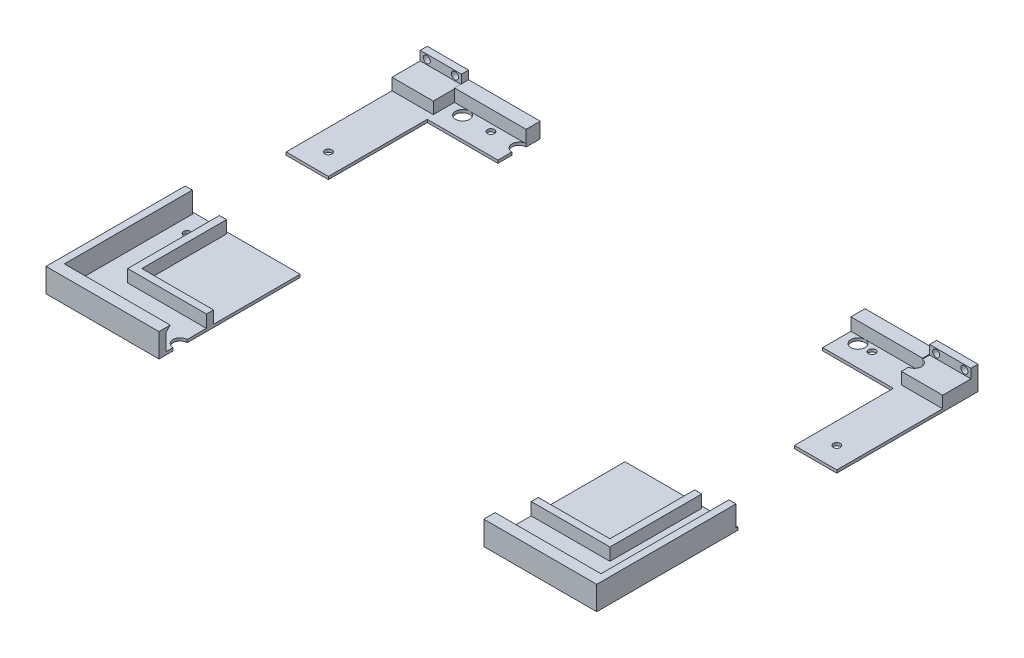
SolidWorks part; units mm, degrees
other "Laptop Holder C"
other "Laptop Holder B"
other "Laptop Holder A"
other "Laptop Holder D"
ref_plane "Front Plane" through (0, 0, 0) normal (0, 0, 1) x (1, 0, 0)
ref_plane "Top Plane" through (0, 0, 0) normal (0, 1, 0) x (1, 0, 0)
ref_plane "Right Plane" through (0, 0, 0) normal (1, 0, 0) x (0, 0, -1)
sketch "Sketch1" plane through (0, 0, 0) normal (0, 1, 0) x (1, 0, 0)
  line L1 (-195, -135) -> (195, -135)
  line L2 (-195, -135) -> (-195, 135)
  line L3 (-195, 135) -> (195, 135)
  line L4 (195, -135) -> (195, 135)
  line L5 (-195, -135) -> (195, 135) construction
  line L6 (-195, 135) -> (195, -135) construction
  point P0 (0, 0)
  dimension "D1" = 390
  dimension "D2" = 270
extrude "Boss-Extrude1" add sketch "Sketch1" along normal blind 16.825
sketch "Sketch2" plane through (0, 16.825, 0) normal (0, 1, 0) x (1, 0, 0)
  line L0 (195, 135) -> (-195, 135) construction
  line L1 (-165.75, -96.4) -> (165.75, -96.4)
  line L2 (-165.75, -96.4) -> (-165.75, 135)
  line L3 (-165.75, 135) -> (165.75, 135)
  line L4 (165.75, -96.4) -> (165.75, 135)
  line L5 (-165.75, -96.4) -> (165.75, 135) construction
  line L6 (-165.75, 135) -> (165.75, -96.4) construction
  point P0 (0, 19.3)
  dimension "D1" = 331.5
  dimension "D2" = 231.4
extrude "Cut-Extrude1" cut sketch "Sketch2" against normal blind 14.825
sketch "Sketch3" plane through (0, 16.825, 0) normal (0, 1, 0) x (1, 0, 0)
  line L0 (195, 135) -> (165.75, 135) construction
  line L1 (-195, -36.4) -> (195, -36.4)
  line L2 (-195, -36.4) -> (-195, 110)
  line L3 (-195, 110) -> (195, 110)
  line L4 (195, -36.4) -> (195, 110)
  line L5 (-195, -36.4) -> (195, 110) construction
  line L6 (-195, 110) -> (195, -36.4) construction
  line L7 (195, -135) -> (195, 135) construction
  line L8 (165.75, -96.4) -> (165.75, 135) construction
  line L9 (195, -36.4) -> (170.75, -36.4)
  line L11 (190, -130) -> (170.75, -130)
  line L12 (170.75, -36.4) -> (170.75, -130)
  line L13 (170.75, -130) -> (0, -130)
  line L14 (170.75, -130) -> (170.75, -101.4)
  line L15 (170.75, -101.4) -> (0, -101.4)
  line L16 (0, -130) -> (0, -101.4)
  line L17 (-165.75, -96.4) -> (165.75, -96.4) construction
  line L18 (-195, -135) -> (195, -135) construction
  line L19 (190, -130) -> (190, -36.4)
  line L20 (170.75, -36.4) -> (190, -36.4)
  line L21 (170.75, -36.4) -> (190, -36.4)
  line L23 (170.75, -36.4) -> (190, -36.4)
  line L24 (170.75, -36.4) -> (170.75, -130)
  line L25 (170.75, -130) -> (190, -130)
  line L26 (190, -36.4) -> (190, -130)
  point P0 (0, 36.8)
  line M20 (165.75, 135) -> (165.75, -96.4)
  line M26 (195, -135) -> (195, 135)
  dimension "D1" = 25
  dimension "D2" = 60
  dimension "D3" = 0
  dimension "D4" = 5
  dimension "D5" = 5
  dimension "D6" = 5
  dimension "D7" = 5
extrude "Cut-Extrude2" cut sketch "Sketch3" against normal up to vertex (14.825 mm away) contours L16 L13 L12 L15 | L11 L19 L1 L12 | L3 L1 L9 M20 M26 up to point (165.75, 2, 96.4)
mirror "Mirror1" about plane through (0, 0, 0) normal (1, 0, 0) of "Cut-Extrude2"
sketch "Sketch4" plane through (0, 2, 0) normal (0, 1, 0) x (1, 0, 0)
  line L1 (-165.75, 125) -> (165.75, 125)
  line L2 (-165.75, 125) -> (-165.75, 135)
  line L3 (-165.75, 135) -> (165.75, 135)
  line L4 (165.75, 125) -> (165.75, 135)
  line L5 (-165.75, 125) -> (165.75, 135) construction
  line L6 (-165.75, 135) -> (165.75, 125) construction
  point P0 (0, 130)
  dimension "D1" = 10
extrude "Boss-Extrude2" add sketch "Sketch4" along normal blind 8.89 contours L2 L1 L4 L3
hole_wizard "CBORE for M5 Hex Head Bolt1" positions "Sketch21" profile "Sketch22" counterbore size "M5" standard "ANSI Metric"
sketch "Sketch21" plane through (0, 0, 0) normal (0, -1, 0) x (-1, 0, 0)
  line L0 (-195, -135) -> (-195, 135) construction
  line L1 (-195, 135) -> (195, 135) construction
  point P0 (-180, 120)
  point P2 (-135, 120)
  point P4 (-180, 50)
  dimension "D1" = 15
  dimension "D2" = 15
  dimension "D3" = 45
  dimension "D4" = 70
sketch "Sketch22" plane through (180, 0, -120) normal (1, 0, 0) x (0, 0, -1)
  line L0 (0, 0) -> (0, 6.3519)
  line L1 (0, 6.3519) -> (2.25, 5)
  line L2 (2.25, 5) -> (2.25, 4.2)
  line L3 (2.25, 4.2) -> (2.5, 4.2)
  line L4 (2.5, 4.2) -> (2.5, 0)
  line L5 (2.5, 0) -> (0, 0)
  line L10 (0, 6.3519) -> (-2.25, 5) construction
  line L11 (0, -6.35) -> (0, 107.95) construction
  dimension "Hole Dia." = 4.5
  dimension "Hole Depth" = 5
  dimension "C'Bore Dia." = 5
  dimension "C'Bore Depth" = 4.2
  dimension "Drill Angle" = 118
mirror "Mirror3" about plane through (0, 0, 0) normal (1, 0, 0) of "CBORE for M5 Hex Head Bolt1" second plane through (0, 0, 0) second plane normal (0, 0, 1)
sketch "Sketch18" plane through (0, 0, 0) normal (0, -1, 0) x (1, 0, 0)
  line L0 (195, -135) -> (-195, -135) construction
  line L1 (-115, 135) -> (115, 135)
  line L2 (-115, 135) -> (-115, -135)
  line L3 (-115, -135) -> (115, -135)
  line L4 (115, 135) -> (115, -135)
  line L5 (-115, 135) -> (115, -135) construction
  line L6 (-115, -135) -> (115, 135) construction
  line L7 (195, 135) -> (195, -135) construction
  line L8 (-195, -35) -> (195, -35)
  line L9 (-195, -35) -> (-195, 35)
  line L10 (-195, 35) -> (195, 35)
  line L11 (195, -35) -> (195, 35)
  line L12 (-195, -35) -> (195, 35) construction
  line L13 (-195, 35) -> (195, -35) construction
  line L15 (-165, -105) -> (165, -105)
  line L16 (-165, -105) -> (-165, -35)
  line L17 (-165, -35) -> (165, -35)
  line L18 (165, -105) -> (165, -35)
  line L19 (-165, -105) -> (165, -35) construction
  line L20 (-165, -35) -> (165, -105) construction
  point P0 (0, 0)
  point P8 (0, -70)
  point P10 (0, 0)
  line M6 (195, -135) -> (195, 135)
  line M7 (195, 135) -> (-195, 135)
  line M8 (-195, 135) -> (-195, -135)
  line M9 (-195, -135) -> (195, -135)
  dimension "D2" = 100
  dimension "D1" = 80
  dimension "D3" = 30
  dimension "D4" = 30
extrude "Cut-Extrude5" cut sketch "Sketch18" against normal through all contours L8 L2 L4 M9 | L10 L8 L2 M8 | L10 L2 L8 L4 | L2 L10 L4 M7 | L10 L4 L8 M6 | L16 L15 L18 L17
sketch "Sketch23" plane through (0, 0, -110) normal (0, 0, 1) x (1, 0, 0)
  line L0 (-165.75, 2) -> (-165.75, 16.825) construction
  line L1 (-195, 16.825) -> (-165.75, 16.825)
  line L2 (-195, 16.825) -> (-195, 10.325)
  line L3 (-195, 10.325) -> (-165.75, 10.325)
  line L4 (-165.75, 16.825) -> (-165.75, 10.325)
  dimension "D1" = 6.5
extrude "Cut-Extrude6" cut sketch "Sketch23" against normal blind 20
hole_wizard "Ø1.0mm Dowel Hole1" positions "Sketch24" profile "Sketch25" hole size "Ø1.0" standard "ANSI Metric" end condition through all
sketch "Sketch24" plane through (0, 0, -130) normal (0, 0, 1) x (1, 0, 0)
  line L0 (-190.375, 13.625) -> (-170.375, 13.625)
  line L6 (-195, 16.825) -> (-165.75, 16.825)
  point P1 (-190.375, 13.625)
  point P2 (-170.375, 13.625)
  point P22 (-180.375, 13.625)
  point P31 (-180.375, 16.825)
  dimension "D1" = 20
  dimension "D2" = 3.2
sketch "Sketch25" plane through (-190.375, 13.625, -130) normal (1, 0, 0) x (0, -1, 0)
  line L0 (0, 0) -> (0, 5)
  line L1 (0, 5) -> (2.5, 5)
  line L2 (2.5, 5) -> (2.5, 0)
  line L5 (2.5, 0) -> (0, 0)
  line L11 (0, -6.35) -> (0, 107.95) construction
  dimension "Thru Hole Dia." = 5
  dimension "Thru Hole Depth" = 5
sketch "Sketch26" plane through (0, 16.825, 0) normal (0, 1, 0) x (1, 0, 0)
  line L6 (115, -101.4) -> (170.75, -101.4)
  line L7 (115, -96.4) -> (115, -101.4)
  line L8 (115, -101.4) -> (170.75, -101.4)
  line L9 (115, -96.4) -> (115, -101.4)
  line L10 (170.75, -101.4) -> (170.75, -36.4)
  line L11 (170.75, -101.4) -> (170.75, -36.4)
  line L18 (115, -96.4) -> (115, -101.4)
  line L19 (115, -101.4) -> (170.75, -101.4)
  line L20 (170.75, -101.4) -> (170.75, -36.4)
  line L21 (170.75, -36.4) -> (165.75, -36.4)
  line L22 (165.75, -36.4) -> (165.75, -96.4)
  line L23 (165.75, -96.4) -> (115, -96.4)
  line L24 (115, -96.4) -> (115, -101.4)
  line L25 (115, -101.4) -> (170.75, -101.4)
  line L26 (170.75, -101.4) -> (170.75, -36.4)
  line L27 (170.75, -36.4) -> (165.75, -36.4)
  line L28 (165.75, -36.4) -> (165.75, -96.4)
  line L29 (165.75, -96.4) -> (115, -96.4)
  line L30 (170.75, -36.4) -> (165.75, -36.4)
  line L31 (170.75, -36.4) -> (165.75, -36.4)
  line L32 (165.75, -36.4) -> (165.75, -96.4)
  line L33 (165.75, -36.4) -> (165.75, -96.4)
  line L34 (-170.75, -101.4) -> (-115, -101.4)
  line L35 (-115, -101.4) -> (-115, -96.4)
  line L36 (-115, -96.4) -> (-165.75, -96.4)
  line L37 (-165.75, -96.4) -> (-165.75, -36.4)
  line L38 (-165.75, -36.4) -> (-170.75, -36.4)
  line L39 (-170.75, -36.4) -> (-170.75, -101.4)
  line L40 (-170.75, -101.4) -> (-115, -101.4)
  line L41 (-115, -101.4) -> (-115, -96.4)
  line L42 (-115, -96.4) -> (-165.75, -96.4)
  line L43 (-165.75, -96.4) -> (-165.75, -36.4)
  line L44 (-165.75, -36.4) -> (-170.75, -36.4)
  line L45 (-170.75, -36.4) -> (-170.75, -101.4)
  line L46 (165.75, -96.4) -> (115, -96.4)
  line L47 (165.75, -96.4) -> (115, -96.4)
  dimension "D1" = 0
  dimension "D2" = 0
  dimension "D3" = 0
extrude "Cut-Extrude7" cut sketch "Sketch26" against normal blind 6
mirror "Mirror5" about plane through (0, 0, 0) normal (1, 0, 0) of "Cut-Extrude6", "Ø1.0mm Dowel Hole1"
sketch "Sketch27" plane through (0, 0, 0) normal (0, 1, 0) x (1, 0, 0)
  line L0 (125, 120) -> (165, 120)
  line L1 (115, 135) -> (165.75, 135) construction
  line L2 (195, 35) -> (195, 110) construction
  line L3 (-155, 120) -> (-115, 120)
  line L4 (-195, 130) -> (-195, 110) construction
  circle A0 centre (165, 120) radius 5
  circle A1 centre (125, 120) radius 5
  circle A2 centre (-155, 120) radius 5
  circle A3 centre (-115, 120) radius 5
  point P4 (145, 120)
  point P11 (-135, 120)
  dimension "D4" = 10
  dimension "D5" = 10
  dimension "D8" = 10
  dimension "D9" = 10
  dimension "D1" = 40
  dimension "D2" = 15
  dimension "D3" = 50
  dimension "D6" = 40
  dimension "D7" = 60
extrude "Cut-Extrude8" cut sketch "Sketch27" along normal through all
mirror "Mirror6" about plane through (0, 0, 0) normal (0, 0, 1) of "Cut-Extrude8"
sketch "Sketch28" plane through (0, 0, 130) normal (0, 0, -1) x (-1, 0, 0)
  line L0 (-190, 13.825) -> (190, 13.825)
  line L1 (190, 2) -> (190, 16.825) construction
  line L2 (115, 16.825) -> (190, 16.825) construction
  line L4 (-190, 2) -> (-115, 2)
  line L5 (-115, 2) -> (-115, 16.825)
  line L6 (-115, 16.825) -> (-190, 16.825)
  line L7 (-190, 16.825) -> (-190, 2)
  line L8 (-190, 2) -> (-115, 2)
  line L9 (-115, 2) -> (-115, 16.825)
  line L10 (-115, 16.825) -> (-190, 16.825)
  line L11 (-190, 16.825) -> (-190, 2)
  line M6 (115, 16.825) -> (115, 2)
  line M8 (190, 2) -> (190, 16.825)
  line M9 (190, 16.825) -> (115, 16.825)
  dimension "D2" = 3
  dimension "D1" = 0
extrude "Boss-Extrude3" add sketch "Sketch28" along normal blind 3 contours L0 M6 M8 M9 | L10 L11 L0 L9
chamfer "Chamfer1" distance 3 angle 45 1 edges at (152.5, 13.825, 127)
chamfer "Chamfer2" distance 3 angle 45 1 edges at (-152.5, 13.825, 127)
